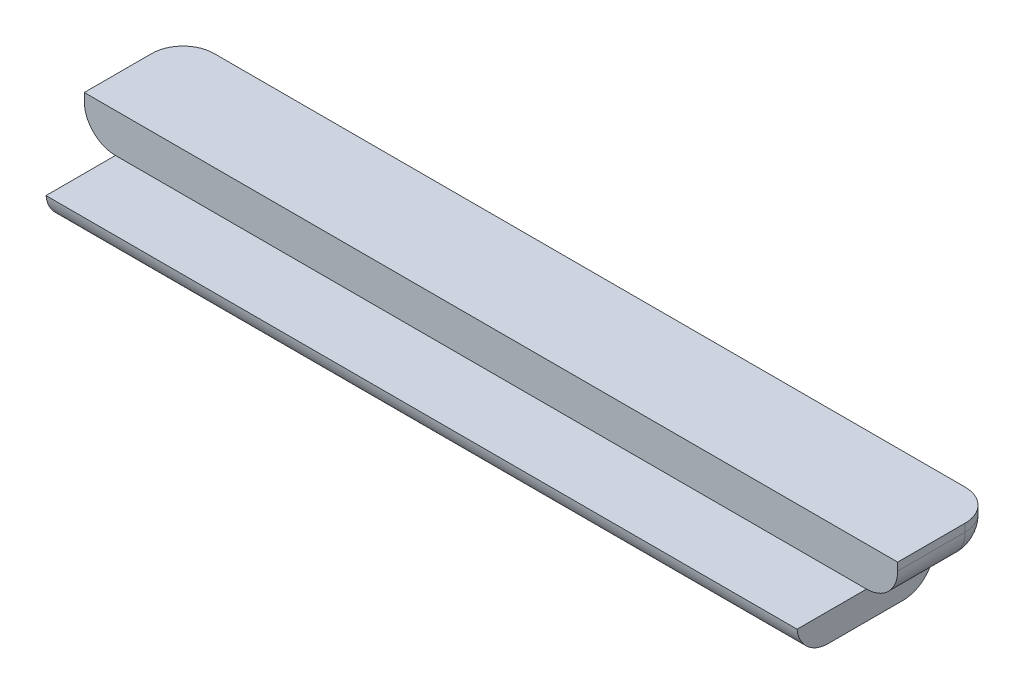
SolidWorks part; units mm, degrees
ref_plane "Front Plane" through (0, 0, 0) normal (0, 0, 1) x (1, 0, 0)
ref_plane "Top Plane" through (0, 0, 0) normal (0, 1, 0) x (1, 0, 0)
ref_plane "Right Plane" through (0, 0, 0) normal (1, 0, 0) x (0, 0, -1)
ref_plane "Plane1" through (0, -35, 0) normal (0, 1, 0) x (1, 0, 0)
sketch "Sketch1" plane through (0, -35, 0) normal (0, 1, 0) x (1, 0, 0)
  line L1 (33.9977, 38.3185) -> (86.1979, 38.3185)
  line L2 (33.9977, 38.3185) -> (33.9977, 31.9864)
  line L3 (33.9977, 31.9864) -> (86.1979, 31.9864)
  line L4 (86.1979, 38.3185) -> (86.1979, 31.9864)
extrude "Boss-Extrude1" add sketch "Sketch1" against normal blind 2.5
fillet "Fillet1" radius 2 1 edges at (60.0978, -37.5, -38.3185)
fillet "Fillet2" radius 2 6 edges at (86.1979, -37.5, -34.1525) (33.9977, -37.5, -34.1525) (86.1979, -36.9142, -37.7328) (33.9977, -36.9142, -37.7328) (86.1979, -35.25, -38.3185) (33.9977, -35.25, -38.3185)
sketch "Sketch4" plane through (0, -37.5, 0) normal (0, -1, 0) x (1, 0, 0)
  line L1 (35.9977, -36.3185) -> (84.1991, -36.3185)
  line L2 (35.9977, -36.3185) -> (35.9977, -27.5295)
  line L3 (35.9977, -27.5295) -> (84.1991, -27.5295)
  line L4 (84.1991, -36.3185) -> (84.1991, -27.5295)
extrude "Boss-Extrude2" add sketch "Sketch4" along normal blind 1.8
fillet "Fillet3" radius 2 1 edges at (60.0984, -39.3, -27.5295)
fillet "Fillet4" radius 2 1 edges at (60.0984, -39.3, -36.3185)
